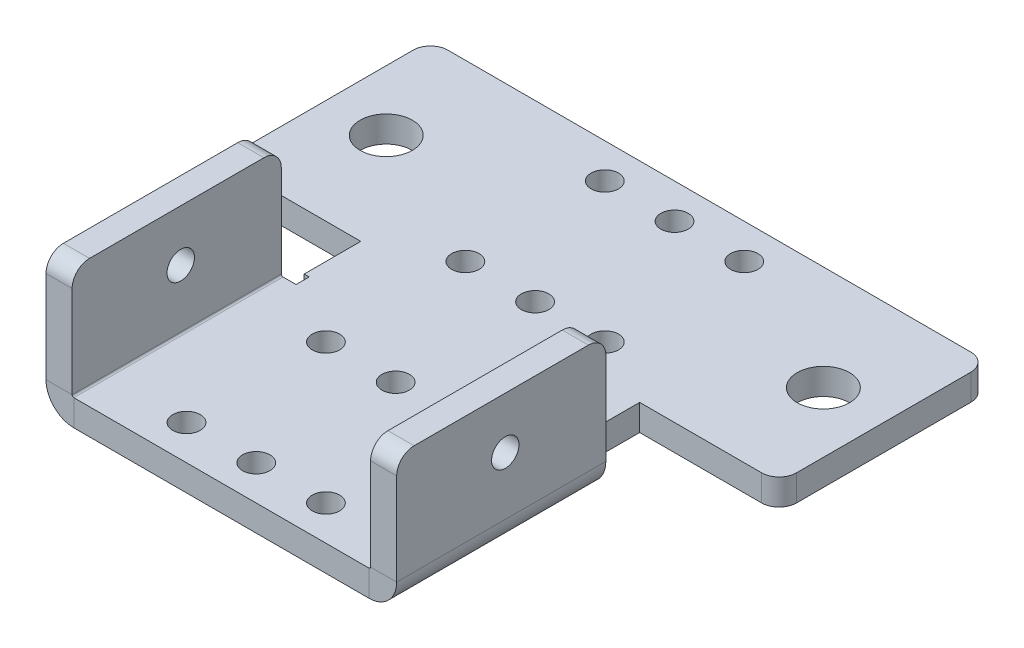
SolidWorks part; units mm, degrees
note: The reader was unsure of these and kept them because the rebuilt part matched: flange length of "Tôle pliée sur arête1".
material "5052-H38, Barre (SS)"
ref_plane "Plan de face" through (0, 0, 0) normal (0, 0, 1) x (1, 0, 0)
ref_plane "Plan de dessus" through (0, 0, 0) normal (0, 1, 0) x (1, 0, 0)
ref_plane "Plan de droite" through (0, 0, 0) normal (1, 0, 0) x (0, 0, -1)
sketch "Esquisse1" plane through (0, 0, 0) normal (0, 1, 0) x (1, 0, 0)
  line L0 (-31.94, -19.05) -> (-31.94, -69.85)
  line L1 (50.8, 19.05) -> (-50.8, 19.05)
  line L2 (50.8, 19.05) -> (50.8, -19.05)
  line L3 (50.8, -19.05) -> (31.94, -19.05)
  line L4 (-50.8, 19.05) -> (-50.8, -19.05)
  line L5 (50.8, 19.05) -> (-50.8, -19.05) construction
  line L6 (50.8, -19.05) -> (-50.8, 19.05) construction
  line L7 (-31.94, -69.85) -> (31.94, -69.85)
  line L8 (31.94, -69.85) -> (31.94, -19.05)
  line L9 (0, 0) -> (0, -69.85) construction
  line L10 (-31.94, -19.05) -> (-50.8, -19.05)
  point P0 (0, 0)
  dimension "D1" = 101.6
  dimension "D2" = 38.1
  dimension "D3" = 88.9
  dimension "D4" = 63.88
base flange "Tôle de base pliée1" sketch "Esquisse1" thickness 4.76 reverse thickness direction no parameters "D1"=0.3125
edge flange "Tôle pliée sur arête1" sketch "Esquisse10" flange profiles "Esquisse10", "Esquisse11" flange angle 90 flange length 25 flange position material inside bend radius 0.3125 thickness 4.76 relief rectangular parameters "D6"=10, "D8"=1
sketch "Esquisse10" plane through (-31.94, 0, 0) normal (-1, 0, 0) x (0, 0, 1)
  line L0 (19.05, -4.76) -> (69.85, -4.76) construction
  line L2 (31.75, 0) -> (31.75, 20.24)
  line L3 (31.75, 20.24) -> (69.85, 20.24)
  line L4 (69.85, 20.24) -> (69.85, 0)
  line L5 (19.05, 0) -> (69.85, 0) construction
  line L6 (31.75, 0) -> (69.85, 0)
  dimension "D1" = 38.1
  dimension "D2" = 25
sketch "Esquisse11" plane through (31.94, 0, 0) normal (1, 0, 0) x (0, 0, -1)
  line L0 (-69.85, 0) -> (-19.05, 0) construction
  line L1 (-69.85, 0) -> (-31.75, 0)
  line L2 (-69.85, 0) -> (-69.85, 20.24)
  line L3 (-69.85, 20.24) -> (-31.75, 20.24)
  line L4 (-31.75, 20.24) -> (-31.75, 0)
  line L5 (-31.75, 0) -> (-31.75, 20.24) construction
  line L6 (-31.75, 20.24) -> (-69.85, 20.24) construction
bend "Pli d'arête1" bend radius 0.3125 bend angle 90 parameters "D5"=1
bend "Pli d'arête2" bend radius 0.3125 bend angle 90 parameters "D5"=2
sketch "Esquisse12" plane through (0, 0, 0) normal (0, 1, 0) x (1, 0, 0)
  line L0 (-24.4875, -29.37) -> (-31.94, -29.37) construction
  line L1 (-31.94, -19.05) -> (-25.4, -19.05)
  line L2 (-31.94, -19.05) -> (-31.94, -29.37)
  line L3 (-31.94, -29.37) -> (-25.4, -29.37)
  line L4 (-25.4, -19.05) -> (-25.4, -29.37)
  line L5 (0, 0) -> (0, -69.85) construction
  line L6 (-26.8675, -69.85) -> (26.8675, -69.85) construction
  line L7 (25.4, -19.05) -> (25.4, -29.37)
  line L8 (31.94, -29.37) -> (25.4, -29.37)
  line L9 (31.94, -19.05) -> (31.94, -29.37)
  line L10 (31.94, -19.05) -> (25.4, -19.05)
  dimension "D1" = 50.8
extrude "Enlèv. mat.-Extru.1" cut sketch "Esquisse12" against normal up to next normal cut yes
fillet "Congé1" radius 3.175 8 edges at (29.56, 20.24, 69.85) (29.56, 20.24, 31.75) (-29.56, 20.24, 31.75) (-29.56, 20.24, 69.85) (50.8, -2.38, -19.05) (50.8, -2.38, 19.05) (-50.8, -2.38, -19.05) (-50.8, -2.38, 19.05)
sketch "Esquisse13" plane through (0, 0, 0) normal (0, 1, 0) x (1, 0, 0)
  line L0 (0, 19.05) -> (0, -69.85) construction
  line L1 (47.625, 19.05) -> (-47.625, 19.05) construction
  line L2 (-26.8675, -69.85) -> (26.8675, -69.85) construction
  line L3 (-50.8, 0) -> (50.8, 0) construction
  line L4 (-50.8, 15.875) -> (-50.8, -15.875) construction
  line L5 (50.8, -15.875) -> (50.8, 15.875) construction
  circle A0 centre (-39.8145, 0) radius 4.7625
  circle A1 centre (39.8145, 0) radius 4.7625
  dimension "D1" = 9.525
  dimension "D2" = 79.629
extrude "Enlèv. mat.-Extru.3" cut sketch "Esquisse13" against normal through all normal cut yes
hole_wizard "Diamètre du perçage Ø5.0 (5)1" positions "Esquisse15" profile "Esquisse14" hole size "Ø5.0" standard "Ansi Metric" end condition through all
sketch "Esquisse15" plane through (0, 0, 0) normal (0, 1, 0) x (1, 0, 0)
  line L0 (-12.7, 12.7) -> (12.7, 12.7) construction
  line L2 (0, 0) -> (0, 12.7) construction
  line L4 (47.625, 19.05) -> (-47.625, 19.05) construction
  point P0 (-12.7, 12.7)
  point P2 (0, 12.7)
  point P4 (12.7, 12.7)
  dimension "D1" = 6.35
  dimension "D2" = 25.4
sketch "Esquisse14" plane through (-12.7, 0, -12.7) normal (1, 0, 0) x (0, 0, 1)
  line L0 (0, 0) -> (0, 4.76)
  line L1 (0, 4.76) -> (2.5, 4.76)
  line L2 (2.5, 4.76) -> (2.5, 0)
  line L5 (2.5, 0) -> (0, 0)
  line L11 (0, -6.35) -> (0, 107.95) construction
  dimension "Diamètre du perçage jusqu'au prochain" = 5
  dimension "Profondeur du perçage jusqu'au prochain" = 4.76
pattern_linear "Répétition linéaire1" count 4 spacing 25.4 along (0, 0, 1) of "Diamètre du perçage Ø5.0 (5)1"
hole_wizard "Diamètre du perçage Ø5.0 (5)2" positions "Esquisse17" profile "Esquisse16" hole size "Ø5.0" standard "Ansi Metric" end condition up to next
sketch "Esquisse17" plane through (-31.94, 0, 0) normal (-1, 0, 0) x (0, 0, 1)
  point P0 (50.0679, 10.8668)
  point P2 (38.4757, -37.8754)
  point P17 (38.4757, -37.8754)
sketch "Esquisse16" plane through (-31.94, 10.8668, 50.0679) normal (0, 1, 0) x (0, 0, 1)
  line L0 (0, 0) -> (0, 4.76)
  line L1 (0, 4.76) -> (2.5, 4.76)
  line L2 (2.5, 4.76) -> (2.5, 0)
  line L5 (2.5, 0) -> (0, 0)
  line L11 (0, -6.35) -> (0, 107.95) construction
  dimension "Diamètre du perçage jusqu'au prochain" = 5
  dimension "Profondeur du perçage jusqu'au prochain" = 4.76
hole_wizard "Diamètre du perçage Ø5.0 (5)3" positions "Esquisse19" profile "Esquisse18" hole size "Ø5.0" standard "Ansi Metric" end condition up to next
sketch "Esquisse19" plane through (31.94, 0, 0) normal (1, 0, 0) x (0, 0, -1)
  circle A0 centre (-50.0679, 10.8668) radius 2.5 construction
  point P0 (-50.0679, 10.8668)
sketch "Esquisse18" plane through (31.94, 10.8668, 50.0679) normal (0, 1, 0) x (0, 0, -1)
  line L0 (0, 0) -> (0, 4.76)
  line L1 (0, 4.76) -> (2.5, 4.76)
  line L2 (2.5, 4.76) -> (2.5, 0)
  line L5 (2.5, 0) -> (0, 0)
  line L11 (0, -6.35) -> (0, 107.95) construction
  dimension "Diamètre du perçage jusqu'au prochain" = 5
  dimension "Profondeur du perçage jusqu'au prochain" = 4.76
sketch "Lignes de pliage1" [suppressed] plane through (0, 0, 0) normal (0, 1, 0) x (1, 0, 0)
sketch "Cube de visualisation1" [suppressed] plane through (0, 0, 0) normal (0, 1, 0) x (1, 0, 0)
sheet metal parameters "Tôlerie1" thickness 4.76 parameters "D1"=0.3125
flat pattern "Etat déplié1" [suppressed]
sketch "Lignes de pliage2" plane through (0, 0, 0) normal (0, 1, 0) x (1, 0, 0)
sketch3d "Cube de visualisation2" [suppressed]
  line L0 (50.8, -69.85, 0) -> (-50.8, -69.85, 0) construction
  line L1 (50.8, 19.05, 0) -> (-50.8, 19.05, 0) construction
  line L2 (50.8, -69.85, 0) -> (50.8, 19.05, 0) construction
  line L3 (-50.8, -69.85, 0) -> (-50.8, 19.05, 0) construction
sheet metal parameters "Tôlerie2" thickness 4.76 parameters "D1"=0.3125
flat pattern "Etat déplié1"
sketch "Lignes de pliage2" plane through (0, 0, 0) normal (0, 1, 0) x (1, 0, 0)
  line L0 (28.9822, -69.85) -> (28.9822, -31.75) construction
  line L1 (-28.9822, -31.75) -> (-28.9822, -69.85) construction
  line L2 (28.9822, -69.85) -> (28.9822, -31.75) construction
  line L3 (-28.9822, -31.75) -> (-28.9822, -69.85) construction
sketch3d "Cube de visualisation2" [suppressed]
  line L0 (-51.0244, -69.85, 0) -> (51.0244, -69.85, 0) construction
  line L1 (-51.0244, 19.05, 0) -> (51.0244, 19.05, 0) construction
  line L2 (-51.0244, -69.85, 0) -> (-51.0244, 19.05, 0) construction
  line L3 (51.0244, -69.85, 0) -> (51.0244, 19.05, 0) construction
bend of the flat pattern "Dépliage-<Pli d'arête1>1"
bend of the flat pattern "Dépliage-<Pli d'arête2>1"
sheet metal parameters "Tôlerie3" thickness 4.76 parameters "D1"=0.3125
flat pattern "Etat déplié1"
sketch "Lignes de pliage2" plane through (0, 0, 0) normal (0, 1, 0) x (1, 0, 0)
  line L0 (28.9822, -69.85) -> (28.9822, -31.75) construction
  line L1 (-28.9822, -31.75) -> (-28.9822, -69.85) construction
  line L2 (28.9822, -69.85) -> (28.9822, -31.75) construction
  line L3 (-28.9822, -31.75) -> (-28.9822, -69.85) construction
sketch3d "Cube de visualisation2" [suppressed]
  line L0 (-51.0244, -69.85, 0) -> (51.0244, -69.85, 0) construction
  line L1 (-51.0244, 19.05, 0) -> (51.0244, 19.05, 0) construction
  line L2 (-51.0244, -69.85, 0) -> (-51.0244, 19.05, 0) construction
  line L3 (51.0244, -69.85, 0) -> (51.0244, 19.05, 0) construction
bend of the flat pattern "Dépliage-<Pli d'arête1>1"
bend of the flat pattern "Dépliage-<Pli d'arête2>1"
sheet metal parameters "Tôlerie5" thickness 4.76 parameters "D1"=0.3125
flat pattern "Etat déplié1"
sketch "Lignes de pliage2" plane through (0, 0, 0) normal (0, 1, 0) x (1, 0, 0)
  line L0 (28.9822, -69.85) -> (28.9822, -31.75) construction
  line L1 (-28.9822, -31.75) -> (-28.9822, -69.85) construction
  line L2 (28.9822, -69.85) -> (28.9822, -31.75) construction
  line L3 (-28.9822, -31.75) -> (-28.9822, -69.85) construction
sketch3d "Cube de visualisation2" [suppressed]
  line L0 (-51.0244, -69.85, 0) -> (51.0244, -69.85, 0) construction
  line L1 (-51.0244, 19.05, 0) -> (51.0244, 19.05, 0) construction
  line L2 (-51.0244, -69.85, 0) -> (-51.0244, 19.05, 0) construction
  line L3 (51.0244, -69.85, 0) -> (51.0244, 19.05, 0) construction
bend of the flat pattern "Dépliage-<Pli d'arête1>1"
bend of the flat pattern "Dépliage-<Pli d'arête2>1"
sheet metal parameters "Tôlerie6" thickness 4.76 parameters "D1"=0.3125
flat pattern "Etat déplié1"
sketch "Lignes de pliage2" plane through (0, 0, 0) normal (0, 1, 0) x (1, 0, 0)
  line L0 (28.9822, -69.85) -> (28.9822, -31.75) construction
  line L1 (-28.9822, -31.75) -> (-28.9822, -69.85) construction
  line L2 (28.9822, -69.85) -> (28.9822, -31.75) construction
  line L3 (-28.9822, -31.75) -> (-28.9822, -69.85) construction
sketch3d "Cube de visualisation2" [suppressed]
  line L0 (-51.0244, -69.85, 0) -> (51.0244, -69.85, 0) construction
  line L1 (-51.0244, 19.05, 0) -> (51.0244, 19.05, 0) construction
  line L2 (-51.0244, -69.85, 0) -> (-51.0244, 19.05, 0) construction
  line L3 (51.0244, -69.85, 0) -> (51.0244, 19.05, 0) construction
bend of the flat pattern "Dépliage-<Pli d'arête1>1"
bend of the flat pattern "Dépliage-<Pli d'arête2>1"
sheet metal parameters "Tôlerie7" thickness 4.76 parameters "D1"=0.3125
flat pattern "Etat déplié1"
sketch "Lignes de pliage2" plane through (0, 0, 0) normal (0, 1, 0) x (1, 0, 0)
  line L0 (28.9822, -69.85) -> (28.9822, -31.75) construction
  line L1 (-28.9822, -31.75) -> (-28.9822, -69.85) construction
  line L2 (28.9822, -69.85) -> (28.9822, -31.75) construction
  line L3 (-28.9822, -31.75) -> (-28.9822, -69.85) construction
sketch3d "Cube de visualisation2" [suppressed]
  line L0 (-51.0244, -69.85, 0) -> (51.0244, -69.85, 0) construction
  line L1 (-51.0244, 19.05, 0) -> (51.0244, 19.05, 0) construction
  line L2 (-51.0244, -69.85, 0) -> (-51.0244, 19.05, 0) construction
  line L3 (51.0244, -69.85, 0) -> (51.0244, 19.05, 0) construction
bend of the flat pattern "Dépliage-<Pli d'arête1>1"
bend of the flat pattern "Dépliage-<Pli d'arête2>1"
sheet metal parameters "Tôlerie8" thickness 4.76 parameters "D1"=0.3125
flat pattern "Etat déplié1"
sketch "Lignes de pliage2" plane through (0, 0, 0) normal (0, 1, 0) x (1, 0, 0)
  line L0 (28.9822, -69.85) -> (28.9822, -31.75) construction
  line L1 (-28.9822, -31.75) -> (-28.9822, -69.85) construction
  line L2 (28.9822, -69.85) -> (28.9822, -31.75) construction
  line L3 (-28.9822, -31.75) -> (-28.9822, -69.85) construction
sketch3d "Cube de visualisation2" [suppressed]
  line L0 (-51.0244, -69.85, 0) -> (51.0244, -69.85, 0) construction
  line L1 (-51.0244, 19.05, 0) -> (51.0244, 19.05, 0) construction
  line L2 (-51.0244, -69.85, 0) -> (-51.0244, 19.05, 0) construction
  line L3 (51.0244, -69.85, 0) -> (51.0244, 19.05, 0) construction
bend of the flat pattern "Dépliage-<Pli d'arête1>1"
bend of the flat pattern "Dépliage-<Pli d'arête2>1"
sheet metal parameters "Tôlerie9" thickness 4.76 parameters "D1"=0.3125
flat pattern "Etat déplié1"
sketch "Lignes de pliage2" plane through (0, 0, 0) normal (0, 1, 0) x (1, 0, 0)
  line L0 (28.9822, -69.85) -> (28.9822, -31.75) construction
  line L1 (-28.9822, -31.75) -> (-28.9822, -69.85) construction
  line L2 (28.9822, -69.85) -> (28.9822, -31.75) construction
  line L3 (-28.9822, -31.75) -> (-28.9822, -69.85) construction
sketch3d "Cube de visualisation2" [suppressed]
  line L0 (-51.0244, -69.85, 0) -> (51.0244, -69.85, 0) construction
  line L1 (-51.0244, 19.05, 0) -> (51.0244, 19.05, 0) construction
  line L2 (-51.0244, -69.85, 0) -> (-51.0244, 19.05, 0) construction
  line L3 (51.0244, -69.85, 0) -> (51.0244, 19.05, 0) construction
bend of the flat pattern "Dépliage-<Pli d'arête1>1"
bend of the flat pattern "Dépliage-<Pli d'arête2>1"
